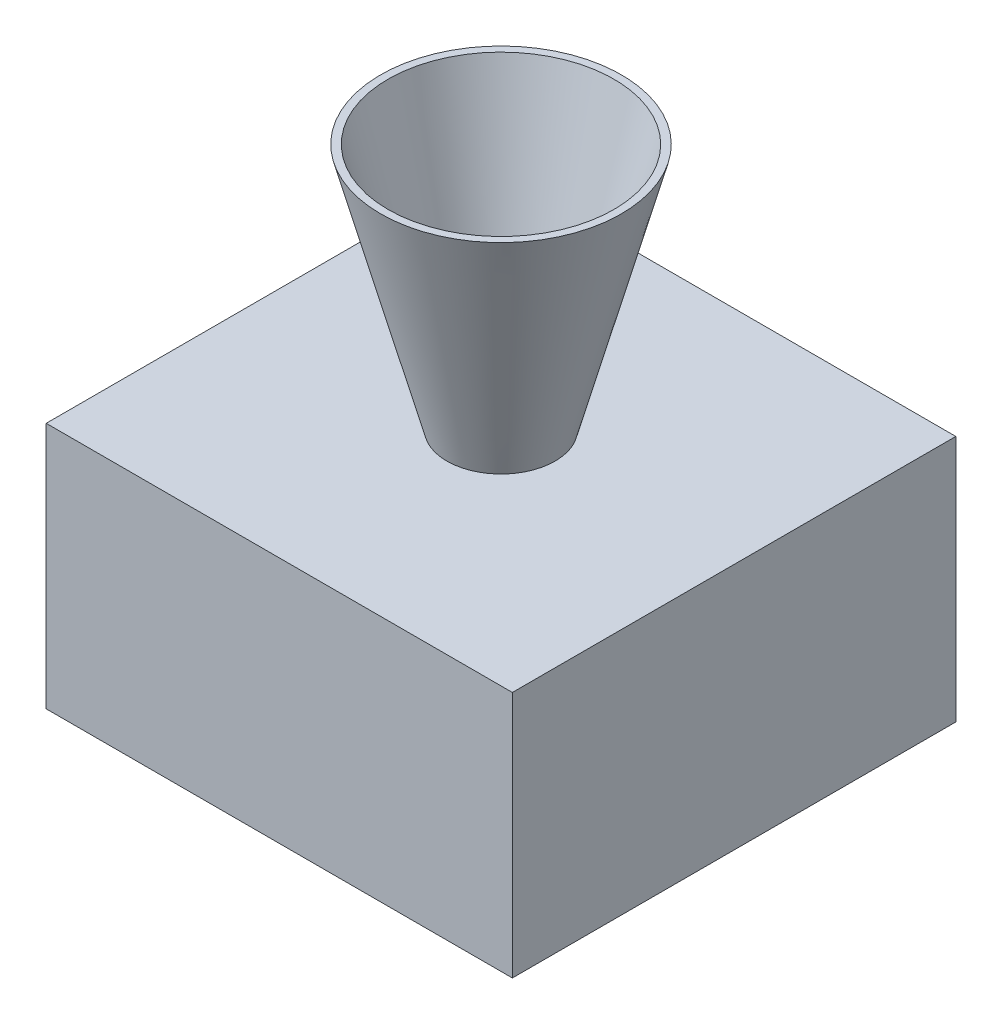
SolidWorks part; units mm, degrees
ref_plane "Front Plane" through (0, 0, 0) normal (0, 0, 1) x (1, 0, 0)
ref_plane "Top Plane" through (0, 0, 0) normal (0, 1, 0) x (1, 0, 0)
ref_plane "Right Plane" through (0, 0, 0) normal (1, 0, 0) x (0, 0, -1)
sketch "Sketch1" plane through (0, 0, 0) normal (0, 1, 0) x (1, 0, 0)
  line L1 (-82, 78) -> (82, 78)
  line L2 (-82, 78) -> (-82, -78)
  line L3 (-82, -78) -> (82, -78)
  line L4 (82, 78) -> (82, -78)
  line L5 (-82, 78) -> (82, -78) construction
  line L6 (-82, -78) -> (82, 78) construction
  point P0 (0, 0)
  dimension "D1" = 164
  dimension "D2" = 156
extrude "Boss-Extrude2" add sketch "Sketch1" along normal blind 87 contours L1 L4 L3 L2
sketch "Sketch2" plane through (0, 87, 0) normal (0, 1, 0) x (1, 0, 0)
  circle A0 centre (0, 0) radius 19.05
  point P2 (0, 0)
extrude "Boss-Extrude3" add sketch "Sketch2" along normal blind 87 draft 15 contours A0 draft outward yes
shell "Shell1" thickness 2.54 removed face at (0, 174, 42.3616)
